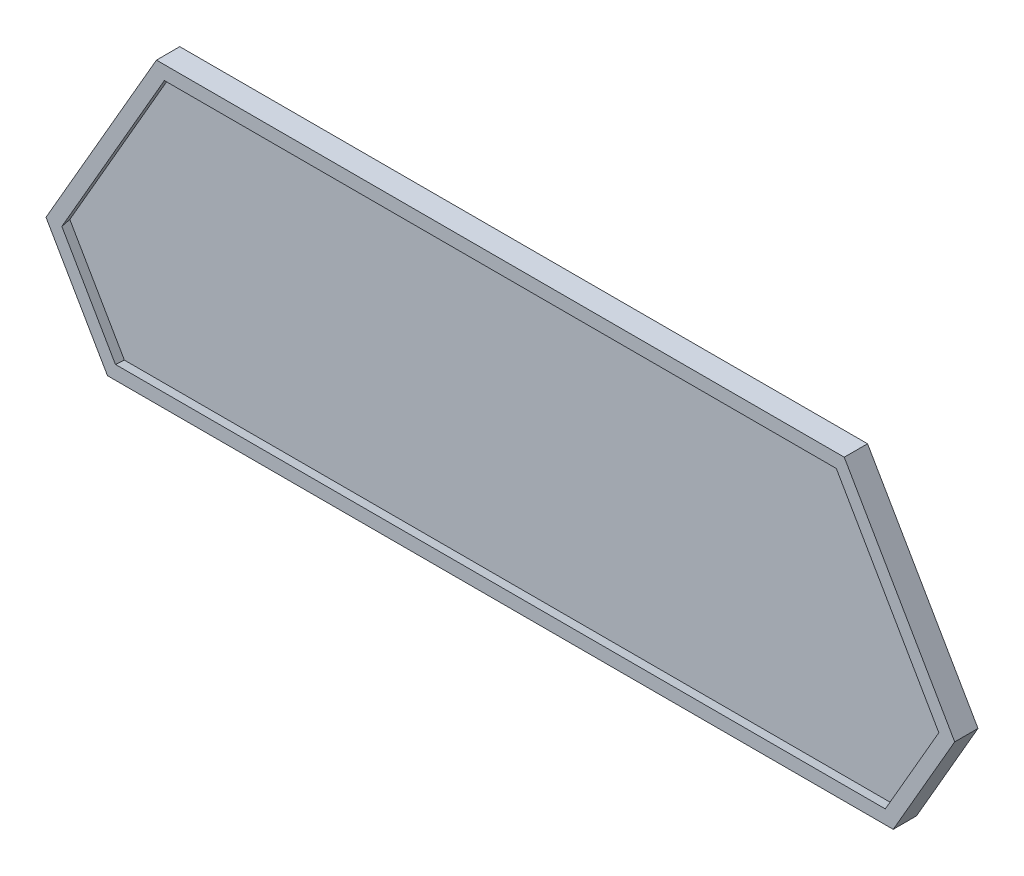
SolidWorks part; units mm, degrees
ref_plane "Plan de face" through (0, 0, 0) normal (0, 0, 1) x (1, 0, 0)
ref_plane "Plan de dessus" through (0, 0, 0) normal (0, 1, 0) x (1, 0, 0)
ref_plane "Plan de droite" through (0, 0, 0) normal (1, 0, 0) x (0, 0, -1)
sketch "Esquisse1" plane through (0, 0, 0) normal (0, 0, 1) x (1, 0, 0)
  line L30 (32.25, -42.5625) -> (2.7, -42.5625)
  line L31 (32.25, -44.0446) -> (32.25, -42.5625)
  line L32 (42.75, -44.0446) -> (32.25, -44.0446)
  line L33 (42.75, -42.5625) -> (42.75, -44.0446)
  line L34 (57.7649, -42.5625) -> (42.75, -42.5625)
  line L35 (65.7427, -28.7446) -> (57.7649, -42.5625)
  line L36 (50.4068, -2.1821) -> (65.7427, -28.7446)
  line L37 (-50.4068, -2.1821) -> (50.4068, -2.1821)
  line L38 (-65.7427, -28.7446) -> (-50.4068, -2.1821)
  line L39 (-57.7649, -42.5625) -> (-65.7427, -28.7446)
  line L40 (-42.75, -42.5625) -> (-57.7649, -42.5625)
  line L41 (-42.75, -44.0446) -> (-42.75, -42.5625)
  line L42 (-32.25, -44.0446) -> (-42.75, -44.0446)
  line L43 (-32.25, -42.5625) -> (-32.25, -44.0446)
  line L44 (-2.7, -42.5625) -> (-32.25, -42.5625)
  line L45 (-2.7, -44.7446) -> (-2.7, -42.5625)
  line L46 (-59.0248, -44.7446) -> (-2.7, -44.7446)
  line L47 (-68.2624, -28.7446) -> (-59.0248, -44.7446)
  line L48 (-51.6667, 0) -> (-68.2624, -28.7446)
  line L49 (51.6667, 0) -> (-51.6667, 0)
  line L50 (68.2624, -28.7446) -> (51.6667, 0)
  line L51 (59.0248, -44.7446) -> (68.2624, -28.7446)
  line L52 (2.7, -44.7446) -> (59.0248, -44.7446)
  line L53 (2.7, -42.5625) -> (2.7, -44.7446)
  line L70 (-59.0248, -44.7446) -> (2.7, -44.7446)
  line L71 (-68.2624, -28.7446) -> (-59.0248, -44.7446)
  line L72 (-51.6667, 0) -> (-68.2624, -28.7446)
  line L73 (51.6667, 0) -> (-51.6667, 0)
  line L74 (68.2624, -28.7446) -> (51.6667, 0)
  line L75 (59.0248, -44.7446) -> (68.2624, -28.7446)
  line L76 (2.7, -44.7446) -> (59.0248, -44.7446)
  point P2 (2.54, -44.7446)
  dimension "D1" = 0
extrude "Boss.-Extru.1" add sketch "Esquisse1" along normal blind 2
sketch "Esquisse2" plane through (0, 0, 2) normal (0, 0, 1) x (1, 0, 0)
  line L6 (-68.2624, -28.7446) -> (-59.0248, -44.7446)
  line L7 (-59.0248, -44.7446) -> (59.0248, -44.7446)
  line L8 (59.0248, -44.7446) -> (68.2624, -28.7446)
  line L9 (68.2624, -28.7446) -> (51.6667, 0)
  line L10 (51.6667, 0) -> (-51.6667, 0)
  line L11 (-51.6667, 0) -> (-68.2624, -28.7446)
  line L12 (-68.2624, -28.7446) -> (-59.0248, -44.7446)
  line L13 (-59.0248, -44.7446) -> (59.0248, -44.7446)
  line L14 (59.0248, -44.7446) -> (68.2624, -28.7446)
  line L15 (68.2624, -28.7446) -> (51.6667, 0)
  line L16 (51.6667, 0) -> (-51.6667, 0)
  line L17 (-51.6667, 0) -> (-68.2624, -28.7446)
  dimension "D1" = 0
extrude "Extru.-Mince1" add sketch "Esquisse2" along normal blind 1.5 draft 10 thin draft outward yes thin type one direction reverse wall 1.8
sketch "Esquisse3" plane through (0, 0, 0) normal (0, 0, -1) x (-1, 0, 0)
  line L6 (59.0248, -44.7446) -> (68.2624, -28.7446)
  line L7 (68.2624, -28.7446) -> (51.6667, 0)
  line L8 (51.6667, 0) -> (-51.6667, 0)
  line L9 (-51.6667, 0) -> (-68.2624, -28.7446)
  line L10 (-68.2624, -28.7446) -> (-59.0248, -44.7446)
  line L11 (-59.0248, -44.7446) -> (59.0248, -44.7446)
  line L12 (59.0248, -44.7446) -> (68.2624, -28.7446)
  line L13 (68.2624, -28.7446) -> (51.6667, 0)
  line L14 (51.6667, 0) -> (-51.6667, 0)
  line L15 (-51.6667, 0) -> (-68.2624, -28.7446)
  line L16 (-68.2624, -28.7446) -> (-59.0248, -44.7446)
  line L17 (-59.0248, -44.7446) -> (59.0248, -44.7446)
  dimension "D1" = 0
extrude "Enlèv. de mat.-Extru.-Mince1" cut sketch "Esquisse3" against normal through all thin thin type one direction wall 1.9
